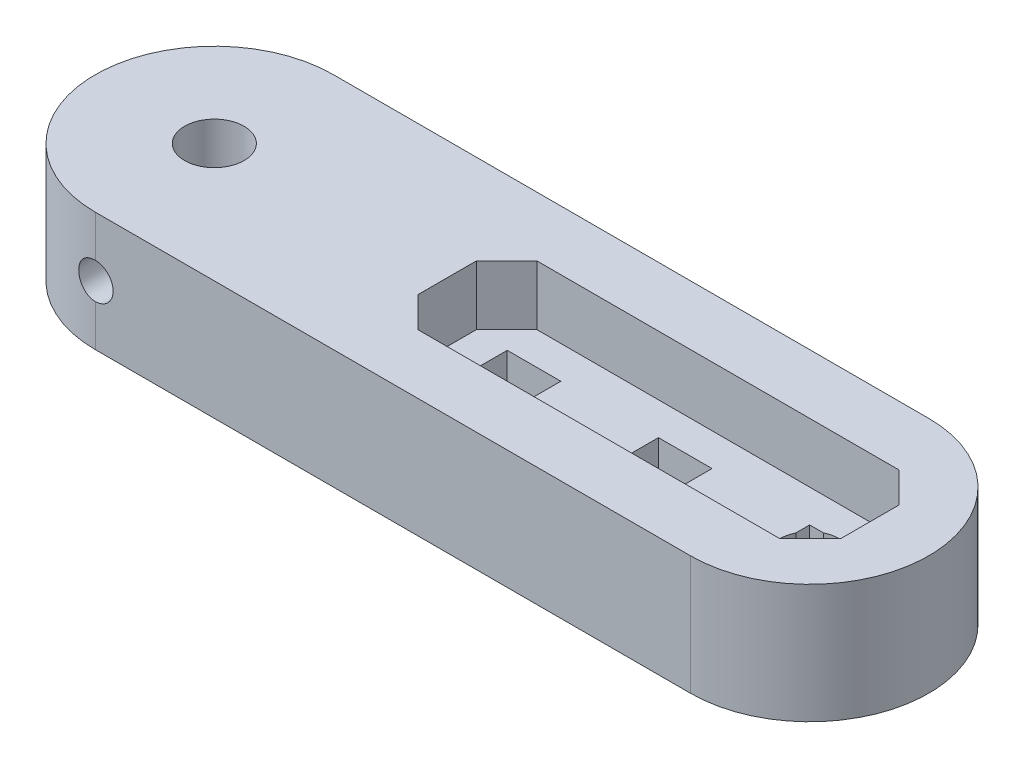
SolidWorks part; units mm, degrees
ref_plane "Front Plane" through (0, 0, 0) normal (0, 0, 1) x (1, 0, 0)
ref_plane "Top Plane" through (0, 0, 0) normal (0, 1, 0) x (1, 0, 0)
ref_plane "Right Plane" through (0, 0, 0) normal (1, 0, 0) x (0, 0, -1)
sketch "Sketch1" plane through (0, 0, 0) normal (0, 1, 0) x (1, 0, 0)
  line L0 (0, -10) -> (-50, -10)
  line L1 (0, 10) -> (-50, 10)
  circle A0 centre (0, 0) radius 2.5
  arc A1 (0, 10) -> (0, -10) centre (0, 0) cw
  circle A2 centre (-50, 0) radius 2.5
  arc A3 (-50, 10) -> (-50, -10) centre (-50, 0) ccw
  dimension "D1" = 5
  dimension "D2" = 50
  dimension "D3" = 20
extrude "Boss-Extrude1" add sketch "Sketch1" along normal blind 10
sketch "Sketch2" plane through (0, 10, 0) normal (0, 1, 0) x (1, 0, 0)
  line L1 (2.25, 2.25) -> (-2.25, 2.25)
  line L2 (2.25, 2.25) -> (2.25, -2.25)
  line L3 (2.25, -2.25) -> (-2.25, -2.25)
  line L4 (-2.25, 2.25) -> (-2.25, -2.25)
  line L5 (2.25, 2.25) -> (-2.25, -2.25) construction
  line L6 (2.25, -2.25) -> (-2.25, 2.25) construction
  line L7 (-10.45, 2.25) -> (-14.95, 2.25)
  line L8 (-10.45, 2.25) -> (-10.45, -2.25)
  line L9 (-10.45, -2.25) -> (-14.95, -2.25)
  line L10 (-14.95, 2.25) -> (-14.95, -2.25)
  line L11 (-10.45, 2.25) -> (-14.95, -2.25) construction
  line L12 (-10.45, -2.25) -> (-14.95, 2.25) construction
  line L13 (-23.15, 2.25) -> (-27.65, 2.25)
  line L14 (-23.15, 2.25) -> (-23.15, -2.25)
  line L15 (-23.15, -2.25) -> (-27.65, -2.25)
  line L16 (-27.65, 2.25) -> (-27.65, -2.25)
  line L17 (-23.15, 2.25) -> (-27.65, -2.25) construction
  line L18 (-23.15, -2.25) -> (-27.65, 2.25) construction
  point P0 (0, 0)
  point P6 (-12.7, 0)
  point P11 (-25.4, 0)
  point P16 (0, 0)
  point P17 (-28.9582, 3.5582)
  dimension "D1" = 12.7
  dimension "D2" = 12.7
  dimension "D3" = 4.5
extrude "Cut-Extrude1" cut sketch "Sketch2" against normal through all
sketch "Sketch3" plane through (0, 10, 0) normal (0, 1, 0) x (1, 0, 0)
  line L0 (-27.91, 5) -> (-30.45, 2.46)
  line L1 (-30.45, 2.46) -> (-30.45, -2.46)
  line L2 (-27.91, 5) -> (2.51, 5)
  line L3 (5.05, 2.46) -> (5.05, -2.46)
  line L4 (-27.91, -5) -> (2.51, -5)
  line L5 (-30.45, 5) -> (5.05, -5) construction
  line L6 (5.05, 5) -> (-30.45, -5) construction
  line L7 (-30.45, -2.46) -> (-27.91, -5)
  line L8 (5.05, -2.46) -> (2.51, -5)
  line L9 (2.51, 5) -> (5.05, 2.46)
  line L10 (-14.95, 2.25) -> (-10.45, -2.25) construction
  line L11 (-27.65, 2.25) -> (-27.65, -2.25) construction
  point P0 (-12.7, 0)
  point P17 (-12.7, 0)
  point P20 (-30.45, 2.25)
  dimension "D1" = 10
  dimension "D2" = 35.5
  dimension "D3" = 2.54
  dimension "D4" = 2.54
  dimension "D5" = 2.54
  dimension "D6" = 2.54
  dimension "D7" = 2.54
  dimension "D8" = 2.54
  dimension "D9" = 2.54
  dimension "D10" = 2.54
extrude "Cut-Extrude2" cut sketch "Sketch3" against normal blind 5
sketch "Sketch4" plane through (0, 0, 10) normal (0, 0, 1) x (1, 0, 0)
  line L1 (-50, 10) -> (-50, 0) construction
  circle A0 centre (-50, 5) radius 1.5
  point P2 (-50, 4.7427)
  point P5 (0, 0)
  point P6 (0, 0)
  point P7 (-50, 5)
  dimension "D1" = 3
extrude "Cut-Extrude3" cut sketch "Sketch4" against normal blind 9 contours A0
